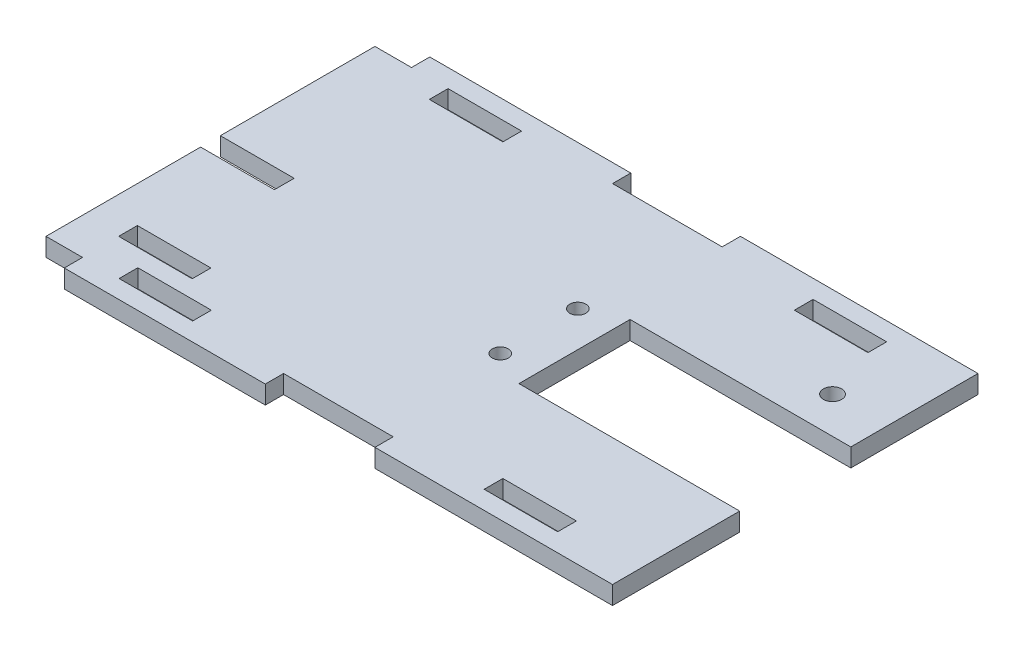
SolidWorks part; units mm, degrees
ref_plane "Front Plane" through (0, 0, 0) normal (0, 0, 1) x (1, 0, 0)
ref_plane "Top Plane" through (0, 0, 0) normal (0, 1, 0) x (1, 0, 0)
ref_plane "Right Plane" through (0, 0, 0) normal (1, 0, 0) x (0, 0, -1)
sketch "Sketch1" plane through (0, 0, 0) normal (0, 1, 0) x (1, 0, 0)
  line L0 (0, 63.5) -> (203.2, 63.5) construction
  line L1 (0, 0) -> (203.2, 0)
  line L2 (0, 0) -> (0, 60.071)
  line L3 (0, 127) -> (203.2, 127)
  line L4 (203.2, 0) -> (203.2, 44.196)
  line L5 (202.946, 82.55) -> (126.746, 82.55) construction
  line L7 (202.946, 44.45) -> (126.746, 44.45) construction
  line L8 (126.746, 82.55) -> (126.746, 44.45) construction
  line L9 (203.2, 82.804) -> (126.492, 82.804)
  line L10 (126.492, 82.804) -> (126.492, 44.196)
  line L11 (203.2, 44.196) -> (126.492, 44.196)
  line L12 (203.2, 60.579) -> (203.2, 53.721)
  line L13 (0, 66.929) -> (25.654, 66.929)
  line L14 (0, 66.675) -> (25.4, 66.675) construction
  line L16 (0, 60.325) -> (25.4, 60.325) construction
  line L17 (25.4, 66.675) -> (25.4, 60.325) construction
  line L22 (25.654, 66.929) -> (25.654, 60.071)
  line L23 (0, 60.071) -> (25.654, 60.071)
  line L27 (0, 66.929) -> (0, 127)
  line L28 (203.2, 82.804) -> (203.2, 127)
  line L29 (203.2, 53.721) -> (203.2, 60.579)
  line L30 (203.2, 82.804) -> (203.2, 44.196) construction
  line L31 (202.946, 82.55) -> (202.946, 44.45) construction
  dimension "D1" = 203.2
  dimension "D2" = 127
  dimension "D4" = 38.1
  dimension "D5" = 76.2
  dimension "D9" = 25.4
  dimension "D10" = 6.35
  dimension "D6" = 0.254
  dimension "D11" = 0.254
extrude "Boss-Extrude1" add sketch "Sketch1" along normal blind 6.35 contours L28 L3 L27 L13 L22 L23 L2 L1 L4 L11 L10 L9 region at (94.0263, 0, -63.5)
sketch "Sketch4" plane through (0, 6.35, 0) normal (0, 1, 0) x (1, 0, 0)
  line L1 (25.4762, 6.4262) -> (50.8762, 6.4262) construction
  line L2 (25.4762, 6.4262) -> (25.4762, 12.7762) construction
  line L3 (25.4762, 12.7762) -> (50.8762, 12.7762) construction
  line L4 (50.8762, 6.4262) -> (50.8762, 12.7762) construction
  line L6 (101.6, 0) -> (101.6, 127) construction
  line L8 (0, 63.5) -> (196.85, 63.5) construction
  line L9 (0, 66.929) -> (0, 60.071)
  line L16 (152.3238, 6.4262) -> (152.3238, 12.7762) construction
  line L17 (177.7238, 12.7762) -> (152.3238, 12.7762) construction
  line L18 (177.7238, 6.4262) -> (177.7238, 12.7762) construction
  line L19 (177.7238, 6.4262) -> (152.3238, 6.4262) construction
  line L20 (177.7238, 120.5738) -> (152.3238, 120.5738) construction
  line L21 (177.7238, 120.5738) -> (177.7238, 114.2238) construction
  line L22 (177.7238, 114.2238) -> (152.3238, 114.2238) construction
  line L23 (152.3238, 120.5738) -> (152.3238, 114.2238) construction
  line L24 (50.8762, 120.5738) -> (50.8762, 114.2238) construction
  line L25 (25.4762, 114.2238) -> (50.8762, 114.2238) construction
  line L26 (25.4762, 120.5738) -> (25.4762, 114.2238) construction
  line L27 (25.4762, 120.5738) -> (50.8762, 120.5738) construction
  line L28 (50.9524, 120.65) -> (50.9524, 114.1476)
  line L29 (25.4, 114.1476) -> (50.9524, 114.1476)
  line L30 (25.4, 120.65) -> (25.4, 114.1476)
  line L31 (25.4, 120.65) -> (50.9524, 120.65)
  line L32 (177.8, 120.65) -> (152.2476, 120.65)
  line L33 (152.2476, 120.65) -> (152.2476, 114.1476)
  line L34 (177.8, 114.1476) -> (152.2476, 114.1476)
  line L35 (177.8, 120.65) -> (177.8, 114.1476)
  line L36 (25.4, 6.35) -> (50.9524, 6.35)
  line L37 (50.9524, 6.35) -> (50.9524, 12.8524)
  line L38 (25.4, 12.8524) -> (50.9524, 12.8524)
  line L39 (25.4, 6.35) -> (25.4, 12.8524)
  line L40 (152.2476, 6.35) -> (152.2476, 12.8524)
  line L41 (177.8, 12.8524) -> (152.2476, 12.8524)
  line L42 (177.8, 6.35) -> (177.8, 12.8524)
  line L43 (177.8, 6.35) -> (152.2476, 6.35)
  line L44 (12.7, 127) -> (12.7, 120.65)
  line L45 (0, 0) -> (12.7, 0)
  line L46 (0, 0) -> (0, 6.35)
  line L47 (0, 6.35) -> (12.7, 6.35)
  line L48 (12.7, 0) -> (12.7, 6.35)
  line L49 (82.55, 0) -> (120.65, 0)
  line L50 (82.55, 0) -> (82.55, 6.35)
  line L51 (82.55, 6.35) -> (120.65, 6.35)
  line L52 (120.65, 0) -> (120.65, 6.35)
  line L53 (0, 120.65) -> (12.7, 120.65)
  line L54 (0, 127) -> (0, 120.65)
  line L55 (0, 127) -> (12.7, 127)
  line L56 (120.65, 127) -> (120.65, 120.65)
  line L57 (82.55, 120.65) -> (120.65, 120.65)
  line L58 (82.55, 127) -> (82.55, 120.65)
  line L59 (82.55, 127) -> (120.65, 127)
  line L60 (0, 66.929) -> (25.654, 66.929) construction
  line L61 (0, 60.071) -> (25.654, 60.071) construction
  line L62 (0, 0) -> (0, 60.071) construction
  line L63 (0, 0) -> (203.2, 0) construction
  dimension "D2" = 25.4
  dimension "D3" = 6.35
  dimension "D8" = 6.35
  dimension "D9" = 12.7
  dimension "D10" = 6.35
  dimension "D11" = 6.35
  dimension "D12" = 38.1
  dimension "D13" = 25.4
  dimension "D4" = 0.0762
  dimension "D5" = 0.0762
  dimension "D6" = 0.0762
  dimension "D7" = 0.0762
extrude "Cut-Extrude1" cut sketch "Sketch4" against normal through all contours L53 L44 | L31 L30 L29 L28 | L58 L57 L56 | L35 L32 L33 L34 | L43 L42 L41 L40 | L52 L51 L50 | L39 L36 L37 L38 | L48 L47 region at (38.1762, 6.35, -117.3988) region at (165.0238, 6.35, -117.3988) region at (38.1762, 6.35, -9.6012) region at (165.0238, 6.35, -9.6012) region at (6.35, 6.35, -123.825) region at (6.35, 6.35, -3.175) region at (101.6, 6.35, -3.175) region at (101.6, 6.35, -123.825)
sketch "Sketch5" plane through (0, 6.35, 0) normal (0, 1, 0) x (1, 0, 0)
  line L0 (203.2, 82.804) -> (126.492, 82.804) construction
  line L25 (203.2, 127) -> (120.65, 127)
  line L26 (120.65, 127) -> (120.65, 120.65)
  line L27 (120.65, 120.65) -> (82.55, 120.65)
  line L28 (82.55, 120.65) -> (82.55, 127)
  line L29 (82.55, 127) -> (12.7, 127)
  line L30 (12.7, 127) -> (12.7, 120.65)
  line L31 (12.7, 120.65) -> (0, 120.65)
  line L32 (0, 120.65) -> (0, 66.929)
  line L33 (0, 66.929) -> (25.654, 66.929)
  line L34 (25.654, 66.929) -> (25.654, 60.071)
  line L35 (25.654, 60.071) -> (0, 60.071)
  line L36 (0, 60.071) -> (0, 6.35)
  line L37 (0, 6.35) -> (12.7, 6.35)
  line L38 (12.7, 6.35) -> (12.7, 0)
  line L39 (12.7, 0) -> (82.55, 0)
  line L40 (82.55, 0) -> (82.55, 6.35)
  line L41 (82.55, 6.35) -> (120.65, 6.35)
  line L42 (120.65, 6.35) -> (120.65, 0)
  line L43 (120.65, 0) -> (203.2, 0)
  line L44 (203.2, 0) -> (203.2, 44.196)
  line L45 (203.2, 44.196) -> (126.492, 44.196)
  line L46 (126.492, 44.196) -> (126.492, 82.804)
  line L47 (126.492, 82.804) -> (203.2, 82.804)
  line L48 (203.2, 82.804) -> (203.2, 127)
  line L49 (203.2, 127) -> (120.65, 127) construction
  line L50 (120.65, 127) -> (120.65, 120.65) construction
  line L51 (120.65, 120.65) -> (82.55, 120.65) construction
  line L52 (82.55, 120.65) -> (82.55, 127) construction
  line L53 (82.55, 127) -> (12.7, 127) construction
  line L54 (12.7, 127) -> (12.7, 120.65) construction
  line L55 (12.7, 120.65) -> (0, 120.65) construction
  line L56 (0, 120.65) -> (0, 66.929) construction
  line L57 (0, 66.929) -> (25.654, 66.929) construction
  line L58 (25.654, 66.929) -> (25.654, 60.071) construction
  line L59 (25.654, 60.071) -> (0, 60.071) construction
  line L60 (0, 60.071) -> (0, 6.35) construction
  line L61 (0, 6.35) -> (12.7, 6.35) construction
  line L62 (12.7, 6.35) -> (12.7, 0) construction
  line L63 (12.7, 0) -> (82.55, 0) construction
  line L64 (82.55, 0) -> (82.55, 6.35) construction
  line L65 (82.55, 6.35) -> (120.65, 6.35) construction
  line L66 (120.65, 6.35) -> (120.65, 0) construction
  line L67 (120.65, 0) -> (203.2, 0) construction
  line L68 (203.2, 0) -> (203.2, 44.196) construction
  line L69 (203.2, 44.196) -> (126.492, 44.196) construction
  line L70 (126.492, 44.196) -> (126.492, 82.804) construction
  line L71 (126.492, 82.804) -> (203.2, 82.804) construction
  line L72 (203.2, 82.804) -> (203.2, 127) construction
  circle A0 centre (184.15, 95.504) radius 3.175
  dimension "D4" = 6.35
  dimension "D1" = 12.7
  dimension "D3" = 19.05
  dimension "D2" = 0
extrude "Cut-Extrude2" cut sketch "Sketch5" against normal through all
sketch "Sketch6" plane through (0, 0, 0) normal (0, -1, 0) x (1, 0, 0)
  line L0 (180.8055, 0) -> (180.8055, -127) construction
  line L1 (120.65, 0) -> (203.2, 0) construction
  line L2 (120.65, -127) -> (203.2, -127) construction
  line L3 (180.8055, -63.5) -> (71.8356, -63.5) construction
  circle A0 centre (114.173, -50.038) radius 2.7781
  circle A1 centre (114.173, -50.038) radius 2.54 construction
  circle A2 centre (114.173, -76.962) radius 2.7781
  dimension "D1" = 5.5562
extrude "Cut-Extrude3" cut sketch "Sketch6" against normal through all
sketch "Sketch7" plane through (0, 6.35, 0) normal (0, 1, 0) x (1, 0, 0)
  line L0 (0, 6.35) -> (0, 60.071) construction
  line L1 (12.7, 25.4) -> (38.1, 25.4) construction
  line L2 (12.7, 25.4) -> (12.7, 19.05) construction
  line L3 (12.7, 19.05) -> (38.1, 19.05) construction
  line L4 (38.1, 25.4) -> (38.1, 19.05) construction
  line L5 (0, 6.35) -> (12.7, 6.35) construction
  line L6 (12.6238, 25.4762) -> (38.1762, 25.4762)
  line L7 (38.1762, 25.4762) -> (38.1762, 18.9738)
  line L8 (12.6238, 18.9738) -> (38.1762, 18.9738)
  line L9 (12.6238, 25.4762) -> (12.6238, 18.9738)
  dimension "D1" = 6.35
  dimension "D2" = 25.4
  dimension "D3" = 12.7
  dimension "D4" = 12.7
  dimension "D5" = 0.0762
extrude "Cut-Extrude4" cut sketch "Sketch7" against normal through all
